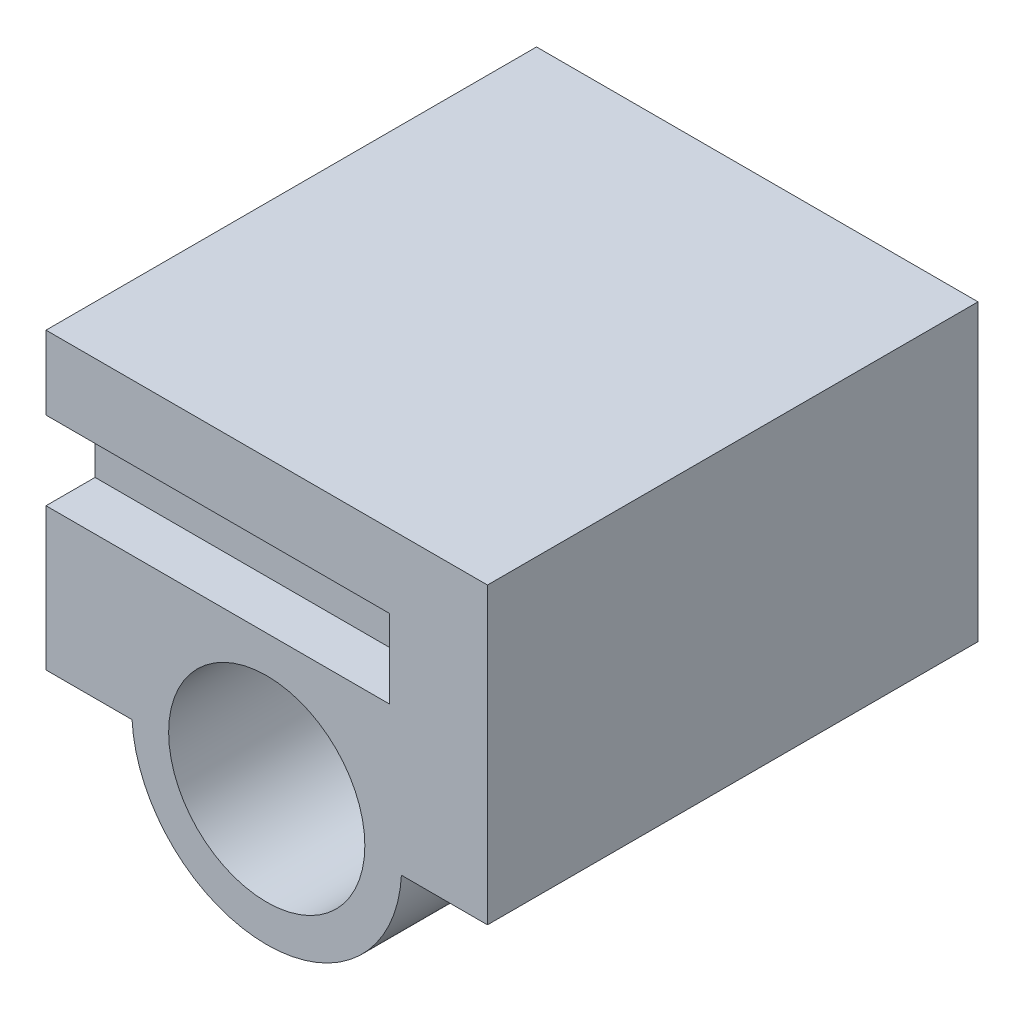
SolidWorks part; units mm, degrees
ref_plane "Front Plane" through (0, 0, 0) normal (0, 0, 1) x (1, 0, 0)
ref_plane "Top Plane" through (0, 0, 0) normal (0, 1, 0) x (1, 0, 0)
ref_plane "Right Plane" through (0, 0, 0) normal (1, 0, 0) x (0, 0, -1)
sketch "Sketch1" plane through (0, 0, 0) normal (0, 0, 1) x (1, 0, 0)
  line L1 (-4.5, 3) -> (4.5, 3)
  line L2 (-4.5, 3) -> (-4.5, -3)
  line L3 (-4.5, -3) -> (4.5, -3)
  line L4 (4.5, 3) -> (4.5, -3)
  line L5 (-4.5, 3) -> (4.5, -3) construction
  line L6 (-4.5, -3) -> (4.5, 3) construction
  point P0 (0, 0)
  dimension "D1" = 9
  dimension "D2" = 6
extrude "Boss-Extrude1" add sketch "Sketch1" along normal blind 10
sketch "Sketch2" plane through (4.5, 0, 0) normal (1, 0, 0) x (0, 0, -1)
  line L0 (-10, -3) -> (-10, 3) construction
  line L1 (-10, 1.5) -> (0, 1.5)
  line L2 (-10, 1.5) -> (-10, -0.1)
  line L3 (-10, -0.1) -> (0, -0.1)
  line L4 (0, 1.5) -> (0, -0.1)
  line L5 (0, -3) -> (0, 3) construction
  line L6 (-10, 3) -> (0, 3) construction
  dimension "D1" = 1.6
  dimension "D2" = 1.5
extrude "Cut-Extrude1" cut sketch "Sketch2" against normal blind 7 from offset 2 offset against normal yes
sketch "Sketch3" plane through (0, 0, 10) normal (0, 0, 1) x (1, 0, 0)
  line L0 (0, 0) -> (0, -3) construction
  line L1 (-4.5, -3) -> (4.5, -3) construction
  line L3 (-4.5, -0.1) -> (2.5, -0.1) construction
  circle A0 centre (0, -2.85) radius 2.75
  dimension "D1" = 5.5
  dimension "D2" = 2.75
extrude "Boss-Extrude2" add sketch "Sketch3" against normal through all
sketch "Sketch4" plane through (0, 0, 10) normal (0, 0, 1) x (1, 0, 0)
  circle A0 centre (0, -2.85) radius 2
  arc A1 (-2.7459, -3) -> (2.7459, -3) centre (0, -2.85) ccw construction
  dimension "D1" = 4
extrude "Cut-Extrude2" cut sketch "Sketch4" against normal blind 4
sketch "Sketch5" plane through (-4.5, 0, 0) normal (-1, 0, 0) x (0, 0, 1)
  line L0 (10, -0.1) -> (0, -0.1) construction
  line L2 (0, -0.1) -> (1, -0.1)
  line L3 (0, -0.1) -> (0, 0.65)
  line L4 (0.15, 0.8) -> (0.85, 0.8)
  line L5 (1, -0.1) -> (1, 0.65)
  line L6 (0, -0.1) -> (0, 1.5) construction
  line L7 (2, -0.1) -> (2, 0.65)
  line L8 (2.15, 0.8) -> (2.85, 0.8)
  line L9 (3, -0.1) -> (3, 0.65)
  line L10 (2, -0.1) -> (3, -0.1)
  line L11 (4, -0.1) -> (4, 0.65)
  line L12 (4.15, 0.8) -> (4.85, 0.8)
  line L13 (5, -0.1) -> (5, 0.65)
  line L14 (4, -0.1) -> (5, -0.1)
  line L15 (6, -0.1) -> (6, 0.65)
  line L16 (6.15, 0.8) -> (6.85, 0.8)
  line L17 (7, -0.1) -> (7, 0.65)
  line L18 (6, -0.1) -> (7, -0.1)
  line L19 (8, -0.1) -> (8, 0.65)
  line L20 (8.15, 0.8) -> (8.85, 0.8)
  line L21 (9, -0.1) -> (9, 0.65)
  line L22 (8, -0.1) -> (9, -0.1)
  arc A0 (0, 0.65) -> (0.15, 0.8) centre (0.15, 0.65) cw
  arc A1 (0.85, 0.8) -> (1, 0.65) centre (0.85, 0.65) cw
  arc A2 (2, 0.65) -> (2.15, 0.8) centre (2.15, 0.65) cw
  arc A3 (2.85, 0.8) -> (3, 0.65) centre (2.85, 0.65) cw
  arc A4 (4, 0.65) -> (4.15, 0.8) centre (4.15, 0.65) cw
  arc A5 (4.85, 0.8) -> (5, 0.65) centre (4.85, 0.65) cw
  arc A6 (6, 0.65) -> (6.15, 0.8) centre (6.15, 0.65) cw
  arc A7 (6.85, 0.8) -> (7, 0.65) centre (6.85, 0.65) cw
  arc A8 (8, 0.65) -> (8.15, 0.8) centre (8.15, 0.65) cw
  arc A9 (8.85, 0.8) -> (9, 0.65) centre (8.85, 0.65) cw
  point P8 (0, 0.8)
  point P11 (1, 0.8)
  dimension "D2" = 0.15
  dimension "D1" = 1
  dimension "D3" = 0.75
  dimension "D4" = 0
  dimension "D6" = 2
  dimension "D5" = 5
extrude "Boss-Extrude3" add sketch "Sketch5" against normal up to next
